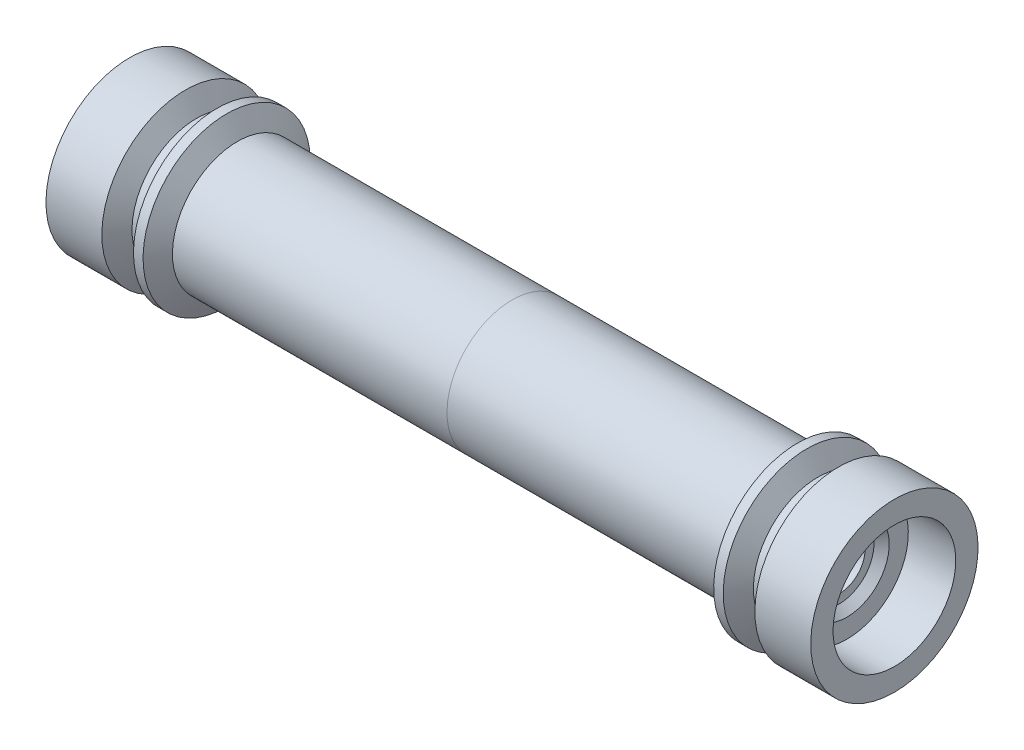
SolidWorks part; units mm, degrees
ref_plane "Front Plane" through (0, 0, 0) normal (0, 0, 1) x (1, 0, 0)
ref_plane "Top Plane" through (0, 0, 0) normal (0, 1, 0) x (1, 0, 0)
ref_plane "Right Plane" through (0, 0, 0) normal (1, 0, 0) x (0, 0, -1)
sketch "Sketch2" plane through (0, 0, 0) normal (0, 0, 1) x (1, 0, 0)
  line L0 (0, 0) -> (0, 28.4375) construction
  line L1 (-25.4, 4.075) -> (-22.25, 4.075) construction
  line L2 (-25.4, 4.075) -> (-25.4, -4.075) construction
  line L3 (-25.4, -4.075) -> (-22.25, -4.075) construction
  line L4 (-22.25, 4.075) -> (-22.25, -4.075) construction
  line L5 (-25.4, 4.075) -> (-22.25, -4.075) construction
  line L6 (-25.4, -4.075) -> (-22.25, 4.075) construction
  line L7 (22.25, 4.5) -> (41.3332, 4.5) construction
  line L8 (22.25, 4.5) -> (22.25, -4.5) construction
  line L9 (22.25, -4.5) -> (41.3332, -4.5) construction
  line L10 (41.3332, 4.5) -> (41.3332, -4.5) construction
  line L11 (22.25, 4.5) -> (41.3332, -4.5) construction
  line L12 (22.25, -4.5) -> (41.3332, 4.5) construction
  line L13 (-25.4, 0) -> (41.3332, 0) construction
  line L14 (-25.4, 5.5562) -> (-21.6882, 5.5562)
  line L21 (-18.2369, 4.318) -> (0, 4.318)
  line L22 (-25.4, 5.5562) -> (-25.4, 4.075)
  line L23 (-25.4, 4.075) -> (-22.25, 4.075)
  line L24 (-22.25, 4.075) -> (-22.25, 0)
  line L25 (-22.25, 0) -> (0, 0)
  line L26 (0, 0) -> (0, 4.318)
  line L27 (-30.6688, -5.5562) -> (-30.6688, 5.5562) construction
  line L28 (-21.6882, 5.5562) -> (-20.955, 4.2862)
  line L29 (-20.955, 4.2862) -> (-20.32, 4.2862)
  line L30 (-25.4, 5.5562) -> (25.4, 5.5562) construction
  line L31 (0, 1.6) -> (-12.5, 1.6)
  line L32 (-12.5, 1.6) -> (-14.1, 0)
  line L33 (-12.5, 1.6) -> (-12.5, -1.6) construction
  line L34 (-12.5, 1.6) -> (12.5, 1.6) construction
  line L35 (-22.25, 1.7145) -> (-15.575, 1.7145)
  line L36 (-15.575, 1.7145) -> (-15.575, 0)
  line L37 (-22.25, 2.805) -> (-21.742, 2.297)
  line L38 (-15.575, 1.7145) -> (-28.575, 1.7145) construction
  line L39 (-15.575, 1.7145) -> (-15.575, -1.7145) construction
  line L40 (-15.575, -1.7145) -> (-28.575, -1.7145) construction
  line L41 (-28.575, 1.7145) -> (-28.575, -1.7145) construction
  line L42 (-21.742, 2.297) -> (-21.742, 0)
  line L46 (-20.32, 4.2862) -> (-19.5868, 5.5562)
  line L47 (-19.5868, 5.5562) -> (-18.9518, 5.5562)
  line L48 (-18.9518, 5.5562) -> (-18.2369, 4.318)
  line L49 (-20.6375, 4.2862) -> (-20.6375, 8.7882) construction
  line L50 (-20.6375, 8.7882) -> (20.6375, 8.7882) construction
  point P0 (-23.825, 0)
  point P5 (31.7916, 0)
  point P27 (-30.6688, 0)
  point P28 (-30.6688, 5.5562)
  point P29 (-12.5, 0)
  point P33 (0, 8.7882)
  point P36 (0, 1.6)
  point P48 (-15.575, 0)
  point P51 (0, 5.5562)
  dimension "D3" = 4.318
  dimension "D4" = 11.1125
  dimension "D5" = 8.15
  dimension "D6" = 60
  dimension "D7" = 0.635
  dimension "D8" = 60
  dimension "D9" = 41.275
  dimension "D10" = 1.27
  dimension "D11" = 50.8
  dimension "D12" = 0.635
  dimension "D13" = 45
  dimension "D14" = 25
  dimension "D15" = 3.2
  dimension "D16" = 3.429
  dimension "D17" = 3.175
  dimension "D18" = 1.27
  dimension "D19" = 0.508
  dimension "D20" = 45
  dimension "D21" = 13
  dimension "D22" = 3.15
revolve "Revolve1" add sketch "Sketch2" angle 360 about L13 region at (-12.3482, 3.069, 0)
mirror "Mirror1" about plane through (0, 0, 0) normal (1, 0, 0) of bodies 101
chamfer "Chamfer1" distance 0.508 angle 45 1 edges at (-25.4, -4.075, 0)
